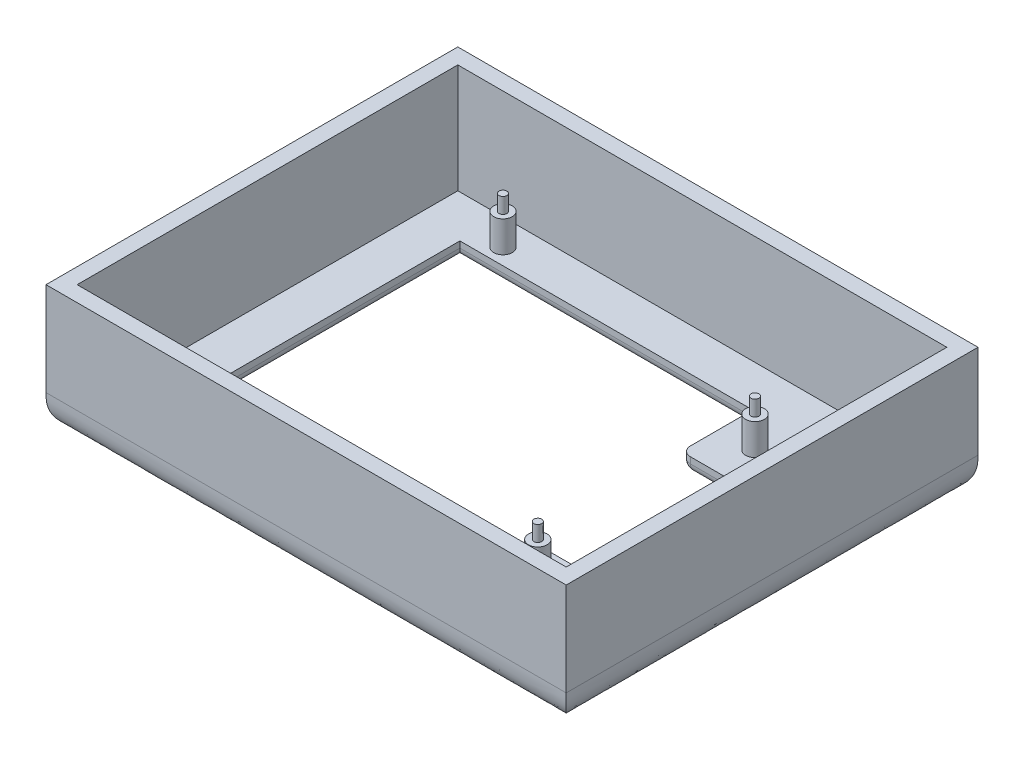
SolidWorks part; units mm, degrees
ref_plane "Ebene vorne" through (0, 0, 0) normal (0, 0, 1) x (1, 0, 0)
ref_plane "Ebene oben" through (0, 0, 0) normal (0, 1, 0) x (1, 0, 0)
ref_plane "Ebene rechts" through (0, 0, 0) normal (1, 0, 0) x (0, 0, -1)
sketch "Skizze1" plane through (0, 0, 0) normal (0, 1, 0) x (1, 0, 0)
  line L0 (-57.4441, 0) -> (108.4227, 0) construction
  line L1 (-83.5, 66.1) -> (83.5, 66.1)
  line L2 (-83.5, 66.1) -> (-83.5, -66.1)
  line L3 (-83.5, -66.1) -> (83.5, -66.1)
  line L4 (83.5, 66.1) -> (83.5, -66.1)
  line L5 (0, 55.397) -> (0, -92.4842) construction
  dimension "D1" = 167
  dimension "D2" = 132.2
extrude "Aufsatz-Linear austragen1" add sketch "Skizze1" along normal blind 80
sketch "Skizze2" plane through (0, 80, 0) normal (0, 1, 0) x (1, 0, 0)
  line L0 (0, 52.0751) -> (0, -71.1014) construction
  line L1 (-78.5, 61.1) -> (78.5, 61.1)
  line L2 (-78.5, 61.1) -> (-78.5, -61.1)
  line L3 (-78.5, -61.1) -> (78.5, -61.1)
  line L4 (78.5, 61.1) -> (78.5, -61.1)
  line L5 (-41.5118, 0) -> (56.2139, 0) construction
  line L6 (-83.5, 66.1) -> (-83.5, -66.1) construction
  line L7 (83.5, 66.1) -> (-83.5, 66.1) construction
  dimension "D1" = 5
  dimension "D2" = 5
extrude "Schnitt-Linear austragen1" cut sketch "Skizze2" against normal blind 75
sketch "Platine" plane through (0, 5, 0) normal (0, 1, 0) x (1, 0, 0)
  line L0 (0, 25.5089) -> (0, -13.445) construction
  line L1 (-17.8492, 0) -> (15.1436, 0) construction
  line L2 (33.515, 54.5281) -> (33.515, -95.4394) construction
  line L3 (58.415, 73.5618) -> (58.415, -76.4057) construction
  line L6 (24.1073, 11.505) -> (87.4465, 11.505) construction
  line L7 (33.8429, -13.445) -> (97.1821, -13.445) construction
  line L8 (-58.415, 56.095) -> (33.515, 56.095)
  line L9 (33.515, 56.095) -> (58.415, 11.505)
  line L10 (58.415, 11.505) -> (58.415, -13.445)
  line L11 (58.415, -13.445) -> (33.515, -56.095)
  line L12 (33.515, -56.095) -> (-58.415, -56.095)
  line L13 (-58.415, -56.095) -> (-58.415, 56.095)
  dimension "D1" = 112.19
  dimension "D2" = 91.93
  dimension "D3" = 24.9
  dimension "D4" = 44.59
  dimension "D5" = 24.95
sketch "Skizze4" plane through (0, 5, 0) normal (0, 1, 0) x (1, 0, 0)
  line L1 (-58.415, -56.095) -> (-58.415, 56.095) construction
  line L2 (-58.415, 56.095) -> (33.515, 56.095) construction
  line L3 (33.515, -56.095) -> (-58.415, -56.095) construction
  line L4 (58.415, 11.505) -> (58.415, -13.445) construction
  circle A0 centre (-55.5494, 52.655) radius 2.985
  circle A1 centre (-55.5494, -53.3587) radius 3
  circle A2 centre (41.2513, -32.9612) radius 3
  circle A3 centre (41.2513, 36.7522) radius 3
  dimension "D9" = 5.97
  dimension "D10" = 6
  dimension "D11" = 6
  dimension "D12" = 6
  dimension "D1" = 2.8656
  dimension "D2" = 3.44
  dimension "D3" = 2.8656
  dimension "D4" = 2.7363
  dimension "D5" = 19.3428
  dimension "D6" = 17.1638
  dimension "D7" = 23.1337
  dimension "D8" = 17.1638
extrude "Aufsatz-Linear austragen2" add sketch "Skizze4" along normal blind 10
sketch "Skizze5" plane through (0, 15, 0) normal (0, 1, 0) x (1, 0, 0)
  circle A0 centre (-55.5494, 52.655) radius 1.25
  circle A1 centre (41.2513, 36.7522) radius 1.25
  circle A2 centre (41.2513, -32.9612) radius 1.25
  circle A3 centre (-55.5494, -53.3587) radius 1.25
  dimension "D1" = 2.5
  dimension "D2" = 2.5
  dimension "D3" = 2.5
  dimension "D4" = 2.5
extrude "Aufsatz-Linear austragen3" add sketch "Skizze5" along normal blind 5
sketch "Skizze6" plane through (0, 0, 0) normal (0, -1, 0) x (1, 0, 0)
  line L0 (29.767, 24.5) -> (29.767, 47.5)
  line L1 (-64.233, 47.5) -> (29.767, 47.5)
  line L2 (-64.233, 47.5) -> (-64.233, -47.5)
  line L3 (-64.233, -47.5) -> (29.767, -47.5)
  line L5 (0, 0) -> (0, 41.5649) construction
  line L6 (0, 0) -> (-36.8563, 0) construction
  line L7 (29.767, 24.5) -> (58.415, 24.5)
  line L8 (58.415, -73.5618) -> (58.415, 76.4057) construction
  line L9 (58.415, 24.5) -> (58.415, -24.5)
  line L10 (58.415, -24.5) -> (29.767, -24.5)
  line L12 (29.767, -24.5) -> (29.767, -47.5)
  dimension "D1" = 95
  dimension "D2" = 94
  dimension "D3" = 23
  dimension "D4" = 94
extrude "Schnitt-Linear austragen2" cut sketch "Skizze6" against normal blind 5
sketch "Skizze10" plane through (0, 80, 0) normal (0, 1, 0) x (1, 0, 0)
  line L0 (0, 0) -> (-140.2518, 0) construction
  line L1 (-140.2518, 0) -> (174.1265, 0) construction
  line L2 (0, 0) -> (0, -99.0125) construction
  line L3 (0, -99.0125) -> (0, 90.3805) construction
  line L4 (-83.5, 66.1) -> (-83.5, -66.1) construction
  line L5 (-83.5, 65) -> (-98.5, 65)
  line L6 (-83.5, 65) -> (-83.5, 55)
  line L7 (-83.5, 55) -> (-98.5, 55)
  line L8 (-98.5, 65) -> (-98.5, 55)
  line L9 (-83.5, -55) -> (-98.5, -55)
  line L10 (-98.5, -65) -> (-98.5, -55)
  line L11 (-83.5, -65) -> (-98.5, -65)
  line L12 (-83.5, -65) -> (-83.5, -55)
  line L13 (83.5, -65) -> (83.5, -55)
  line L14 (83.5, -65) -> (98.5, -65)
  line L15 (98.5, -65) -> (98.5, -55)
  line L16 (83.5, -55) -> (98.5, -55)
  line L17 (98.5, 65) -> (98.5, 55)
  line L18 (83.5, 55) -> (98.5, 55)
  line L19 (83.5, 65) -> (83.5, 55)
  line L20 (83.5, 65) -> (98.5, 65)
  line L21 (91, 65) -> (91, 55) construction
  line L22 (98.5, 60) -> (83.5, 60) construction
  circle A0 centre (91, 60) radius 2.75
  circle A1 centre (91, -60) radius 2.75
  circle A2 centre (-91, -60) radius 2.75
  circle A3 centre (-91, 60) radius 2.75
  dimension "D3" = 5.5
  dimension "D1" = 15
  dimension "D2" = 10
  dimension "D4" = 60
extrude "befestigung" add sketch "Skizze10" against normal blind 20
sketch "Skizze11" plane through (0, 0, -66.1) normal (0, 0, -1) x (-1, 0, 0)
  line L3 (0, 0) -> (0, 80) construction
  line L4 (-83.5, 80) -> (83.5, 80) construction
  line L7 (83.5, 65.6081) -> (98.5, 76.4455)
  line L8 (98.5, 60) -> (98.5, 80) construction
  line L9 (83.5, 80) -> (83.5, 0) construction
  line L10 (83.5, 65.6081) -> (83.5, 60)
  line L11 (83.5, 60) -> (98.5, 60)
  line L12 (98.5, 60) -> (98.5, 76.4455)
  line L13 (-98.5, 60) -> (-98.5, 76.4455)
  line L14 (-83.5, 60) -> (-98.5, 60)
  line L15 (-83.5, 65.6081) -> (-83.5, 60)
  line L16 (-83.5, 65.6081) -> (-98.5, 76.4455)
extrude "Schnitt-Linear austragen9" cut sketch "Skizze11" against normal through all
ref_plane "Ebene1" through (0, 74, 0) normal (0, 1, 0) x (1, 0, 0)
sketch "Skizze13" plane through (0, 74, 0) normal (0, 1, 0) x (1, 0, 0)
  line L0 (0, 0) -> (0, 94.861) construction
  line L1 (0, 94.861) -> (0, -99.5436) construction
  line L2 (96.6502, 0) -> (-112.8768, 0) construction
  circle A0 centre (91, 60) radius 4.5
  circle A1 centre (91, -60) radius 4.5
  circle A2 centre (-91, -60) radius 4.5
  circle A3 centre (-91, 60) radius 4.5
  dimension "D1" = 9
extrude "Schnitt-Linear austragen10" cut sketch "Skizze13" against normal blind 8
fillet "Verrundung3" radius 3 8 edges at (83.5, 65.6081, 60) (83.5, 65.6081, -60) (-83.5, 65.6081, 60) (-83.5, 65.6081, -60) (-98.5, 76.4455, -60) (-98.5, 76.4455, 60) (98.5, 76.4455, -60) (98.5, 76.4455, 60)
fillet "Verrundung4" radius 10 4 edges at (-83.5, 0, 0) (0, 0, -66.1) (0, 0, 66.1) (83.5, 0, 0) curvature continuous yes
fillet "Verrundung5" radius 3 8 edges at (29.767, 0, 36) (44.091, 0, 24.5) (58.415, 0, 0) (44.091, 0, -24.5) (29.767, 0, -36) (-17.233, 0, -47.5) (-64.233, 0, 0) (-17.233, 0, 47.5)
fillet "Verrundung6" radius 3 4 edges at (30.6457, 0.8787, -25.3787) (30.6457, 0.8787, 25.3787) (29.767, 4, -24.5) (29.767, 4, 24.5)
sketch "Skizze14" plane through (0, 80, 0) normal (0, 1, 0) x (1, 0, 0)
  line L1 (-99.5816, 68.6273) -> (100.6844, 68.6273)
  line L2 (-99.5816, 68.6273) -> (-99.5816, -70.1033)
  line L3 (-99.5816, -70.1033) -> (100.6844, -70.1033)
  line L4 (100.6844, 68.6273) -> (100.6844, -70.1033)
extrude "Schnitt-Linear austragen11" cut sketch "Skizze14" against normal blind 40
